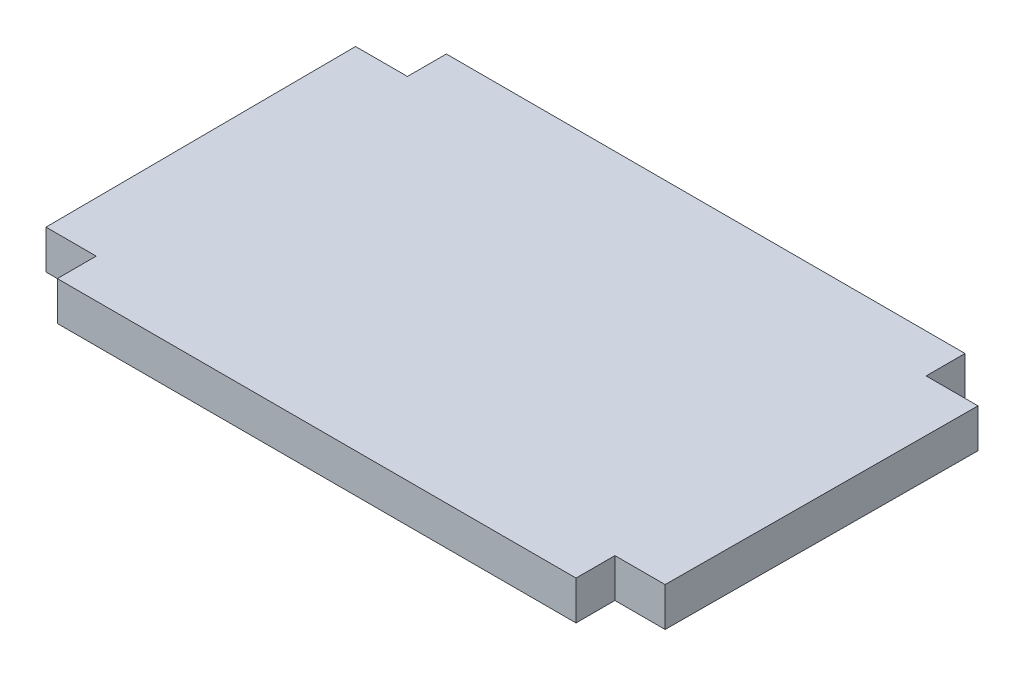
SolidWorks part; units mm, degrees
ref_plane "Alzado" through (0, 0, 0) normal (0, 0, 1) x (1, 0, 0)
ref_plane "Planta" through (0, 0, 0) normal (0, 1, 0) x (1, 0, 0)
ref_plane "Vista lateral" through (0, 0, 0) normal (1, 0, 0) x (0, 0, -1)
sketch "Croquis2" plane through (0, 0, 0) normal (0, 1, 0) x (1, 0, 0)
  line L1 (40, -11.9997) -> (44, -11.9997)
  line L2 (-4, 12) -> (0, 12)
  line L3 (40, 12) -> (40, 15)
  line L4 (40, 15) -> (0, 15)
  line L5 (0, 15) -> (0, 12)
  line L6 (40, 15) -> (40, 12)
  line L7 (0, 12) -> (0, 15)
  line L8 (40, 12) -> (44, 12)
  line L9 (-4, -11.9997) -> (0, -11.9997)
  line L10 (0, -11.9997) -> (0, -14.9997)
  line L11 (-3.8729, -11.9997) -> (-4, 12)
  line L12 (40, -14.9997) -> (40, -11.9997)
  line L13 (0, -14.9997) -> (0, -11.9997)
  line L14 (40, -14.9997) -> (0, -14.9997)
  line L15 (40, -11.9997) -> (40, -14.9997)
  line L19 (43.8729, -11.9997) -> (44, 12)
  dimension "D1" = 40
  dimension "D3" = 4
  dimension "D5" = 4
  dimension "D7" = 24
  dimension "D8" = 24
extrude "Saliente-Extruir1" add sketch "Croquis2" along normal blind 3 contours L19 L5 L11 region at (20, 0, -0.009)
